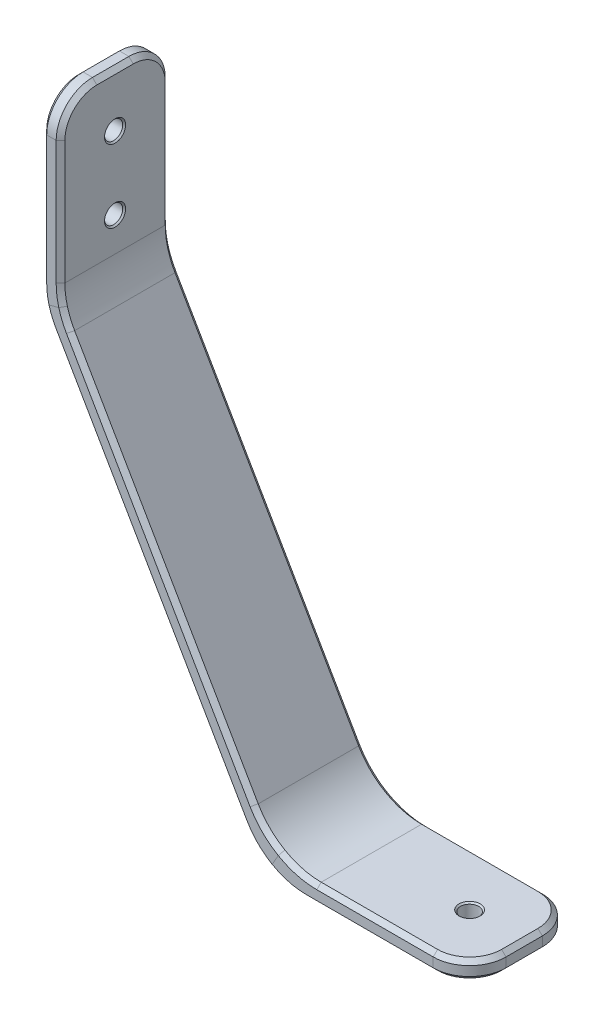
SolidWorks part; units mm, degrees
ref_plane "Front Plane" through (0, 0, 0) normal (0, 0, 1) x (1, 0, 0)
ref_plane "Top Plane" through (0, 0, 0) normal (0, 1, 0) x (1, 0, 0)
ref_plane "Right Plane" through (0, 0, 0) normal (1, 0, 0) x (0, 0, -1)
sketch "Sketch1" plane through (0, 0, 0) normal (0, 0, 1) x (1, 0, 0)
  line L0 (0, 0) -> (0, -31.75)
  line L1 (0, -31.75) -> (38.1, -97.7411)
  line L2 (38.1, -97.7411) -> (73.025, -97.7411)
  dimension "D2" = 76.2
  dimension "D1" = 31.75
  dimension "D3" = 150
  dimension "D4" = 120
  dimension "D5" = 34.925
sketch "Sketch2" plane through (0, 0, 0) normal (0, 1, 0) x (1, 0, 0)
  line L1 (-1.5875, -9.525) -> (1.5875, -9.525)
  line L2 (-1.5875, -9.525) -> (-1.5875, 9.525)
  line L3 (-1.5875, 9.525) -> (1.5875, 9.525)
  line L4 (1.5875, -9.525) -> (1.5875, 9.525)
  line L5 (-1.5875, -9.525) -> (1.5875, 9.525) construction
  line L6 (-1.5875, 9.525) -> (1.5875, -9.525) construction
  point P0 (0, 0)
  dimension "D1" = 3.175
  dimension "D2" = 19.05
sweep "Sweep1" add profiles "Sketch2" path "Sketch1"
hole_wizard "1/8 (0.125) Diameter Hole1" positions "Sketch3" profile "Sketch4" hole size "1/8" standard "ANSI Inch" end condition through all
sketch "Sketch3" plane through (1.5875, 0, 0) normal (1, 0, 0) x (0, 0, -1)
  line L0 (0, -22.0123) -> (0, -31.3246) construction
  line L1 (9.525, -31.3246) -> (-9.525, -31.3246) construction
  line L3 (0, -9.3123) -> (0, 0) construction
  point P0 (0, -9.3123)
  point P2 (0, -22.0123)
  dimension "D1" = 12.7
sketch "Sketch4" plane through (1.5875, -9.3123, 0) normal (0, 1, 0) x (0, 0, -1)
  line L0 (0, 0) -> (0, 3.175)
  line L1 (0, 3.175) -> (1.5875, 3.175)
  line L2 (1.5875, 3.175) -> (1.5875, 0)
  line L5 (1.5875, 0) -> (0, 0)
  line L11 (0, -6.35) -> (0, 107.95) construction
  dimension "Thru Hole Dia." = 3.175
  dimension "Thru Hole Depth" = 3.175
hole_wizard "1/8 (0.125) Diameter Hole2" positions "Sketch5" profile "Sketch6" hole size "1/8" standard "ANSI Inch" end condition through all
sketch "Sketch5" plane through (0, -96.1536, 0) normal (0, 1, 0) x (1, 0, 0)
  line L0 (73.025, -9.525) -> (73.025, 9.525) construction
  point P0 (63.5, 0)
  dimension "D1" = 9.525
sketch "Sketch6" plane through (63.5, -96.1536, 0) normal (1, 0, 0) x (0, 0, 1)
  line L0 (0, 0) -> (0, 3.175)
  line L1 (0, 3.175) -> (1.5875, 3.175)
  line L2 (1.5875, 3.175) -> (1.5875, 0)
  line L5 (1.5875, 0) -> (0, 0)
  line L11 (0, -6.35) -> (0, 107.95) construction
  dimension "Thru Hole Dia." = 3.175
  dimension "Thru Hole Depth" = 3.175
fillet "Fillet1" radius 12.7 4 edges at (-1.5875, -32.1754, 0) (1.5875, -31.3246, 0) (37.1835, -99.3286, 0) (39.0165, -96.1536, 0)
fillet "Fillet2" radius 6.35 4 edges at (73.025, -97.7411, -9.525) (73.025, -97.7411, 9.525) (0, 0, -9.525) (0, 0, 9.525)
chamfer "Chamfer3" distance 0.762 angle 45 40 edges at (16.8156, -64.0505, -9.525) (-0.6208, -33.6325, -9.525) (35.5355, -95.6089, -9.525) (-1.4788, -30.4301, -9.525) (41.2288, -98.8959, -9.525) (-1.5875, -17.5612, -9.525) (55.5954, -99.3286, -9.525) (-1.5875, -1.8599, -7.6651) (71.1651, -99.3286, -7.6651) (-1.5875, 0, 0) (73.025, -99.3286, 0) (-1.5875, -1.8599, 7.6651) (71.1651, -99.3286, 7.6651) (-1.5875, -17.5612, 9.525) (55.5954, -99.3286, 9.525) (-1.4788, -30.4301, 9.525) (41.2288, -98.8959, 9.525) (-0.6208, -33.6325, 9.525) (35.5355, -95.6089, 9.525) (16.8156, -64.0505, 9.525) (19.3197, -62.0377, -9.525) (2.5542, -32.7818, -9.525) (37.3686, -92.4339, -9.525) (1.6962, -29.5794, -9.525) (43.0619, -95.7209, -9.525) (1.5875, -17.1358, -9.525) (56.5119, -96.1536, -9.525) (1.5875, -1.8599, -7.6651) (71.1651, -96.1536, -7.6651) (1.5875, 0, 0) (73.025, -96.1536, 0) (1.5875, -1.8599, 7.6651) (71.1651, -96.1536, 7.6651) (1.5875, -17.1358, 9.525) (56.5119, -96.1536, 9.525) (1.6962, -29.5794, 9.525) (43.0619, -95.7209, 9.525) (2.5542, -32.7818, 9.525) (37.3686, -92.4339, 9.525) (19.3197, -62.0377, 9.525)
chamfer "Chamfer2" distance 0.254 angle 45 6 edges at (1.5875, -22.0123, -1.5875) (-1.5875, -22.0123, -1.5875) (1.5875, -9.3123, -1.5875) (-1.5875, -9.3123, -1.5875) (63.5, -96.1536, 1.5875) (63.5, -99.3286, 1.5875)
